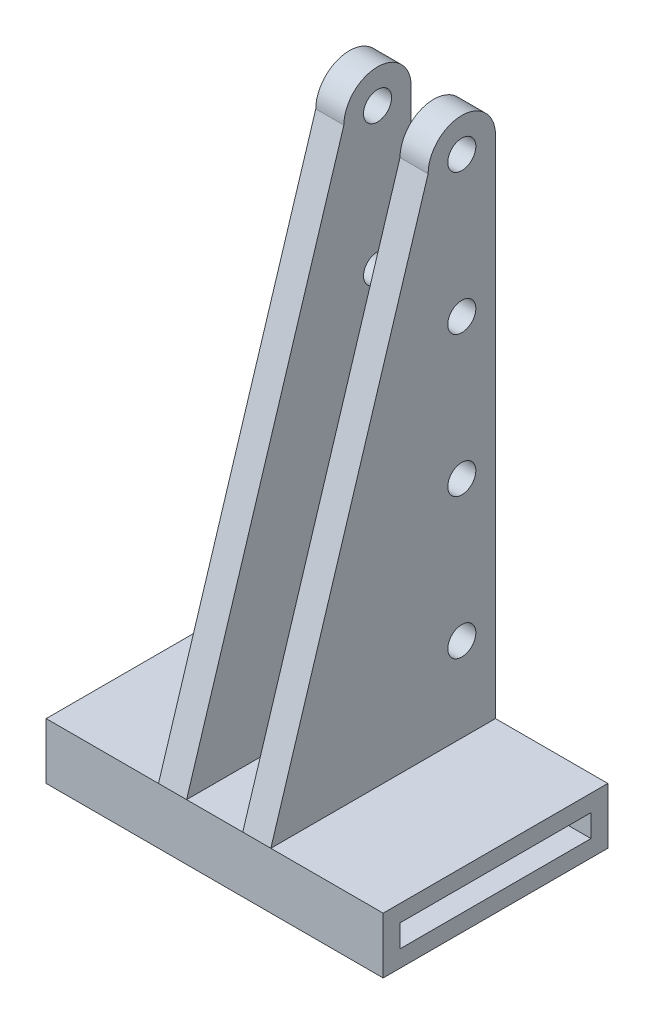
SolidWorks part; units mm, degrees
ref_plane "Front Plane" through (0, 0, 0) normal (0, 0, 1) x (1, 0, 0)
ref_plane "Top Plane" through (0, 0, 0) normal (0, 1, 0) x (1, 0, 0)
ref_plane "Right Plane" through (0, 0, 0) normal (1, 0, 0) x (0, 0, -1)
sketch "Sketch1" plane through (0, 0, 0) normal (0, 1, 0) x (1, 0, 0)
  line L1 (-30, 20) -> (30, 20)
  line L2 (-30, 20) -> (-30, -20)
  line L3 (-30, -20) -> (30, -20)
  line L4 (30, 20) -> (30, -20)
  line L5 (-30, 20) -> (30, -20) construction
  line L6 (-30, -20) -> (30, 20) construction
  point P0 (0, 0)
  dimension "D1" = 60
  dimension "D2" = 40
extrude "Boss-Extrude1" add sketch "Sketch1" along normal blind 10
sketch "Sketch2" plane through (0, 0, 0) normal (1, 0, 0) x (0, 0, -1)
  line L0 (20, 10) -> (-20, 10) construction
  line L1 (20, 10) -> (-20, 10)
  line L2 (20, 10) -> (20, 100)
  line L3 (8, 100) -> (-20, 10)
  line L4 (-20, 10) -> (-20, 0) construction
  arc A0 (20, 100) -> (8, 100) centre (14, 100) ccw
  circle A1 centre (14, 100) radius 2.5
  circle A2 centre (14, 75) radius 2.5
  circle A3 centre (14, 50) radius 2.5
  circle A4 centre (14, 25) radius 2.5
  dimension "D2" = 6
  dimension "D3" = 5
  dimension "D1" = 90
  dimension "D5" = 25
  dimension "D4" = 4
extrude "Boss-Extrude2" add sketch "Sketch2" along normal blind 5 from offset 5 contours L2 A0 L3 L1 A4 A3 A2 A1 region at (0, 47.7522, -5.6653)
extrude "Boss-Extrude3" add sketch "Sketch2<3>" against normal blind 5 from offset 5 contours L2 A0 L3 L1 A4 A3 A2 A1 region at (0, 47.7522, -5.6653) offset against normal yes
sketch "Sketch2<3>" plane through (0, 0, 0) normal (1, 0, 0) x (0, 0, -1) same geometry as "Sketch2"
sketch "Sketch3" plane through (-30, 0, 0) normal (-1, 0, 0) x (0, 0, 1)
  line L8 (-17, 3) -> (17, 3)
  line L9 (17, 3) -> (17, 7)
  line L10 (17, 7) -> (-17, 7)
  line L11 (-17, 7) -> (-17, 3)
  line L12 (-17, 3) -> (17, 3)
  line L13 (17, 3) -> (17, 7)
  line L14 (17, 7) -> (-17, 7)
  line L15 (-17, 7) -> (-17, 3)
  dimension "D1" = 3
extrude "Cut-Extrude1" cut sketch "Sketch3" against normal through all
